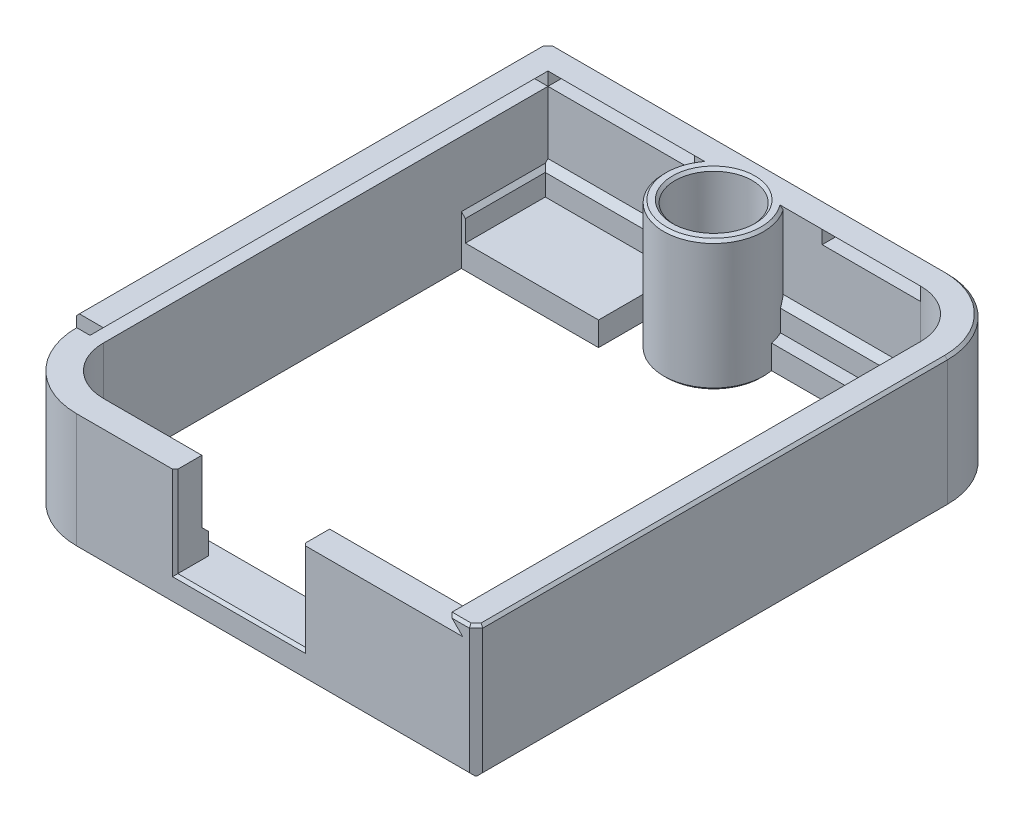
SolidWorks part; units mm, degrees
ref_plane "前视基准面" through (0, 0, 0) normal (0, 0, 1) x (1, 0, 0)
ref_plane "上视基准面" through (0, 0, 0) normal (0, 1, 0) x (1, 0, 0)
ref_plane "右视基准面" through (0, 0, 0) normal (1, 0, 0) x (0, 0, -1)
sketch "草图1" plane through (0, 0, 0) normal (0, 1, 0) x (1, 0, 0)
  line L0 (-23.4673, 10.3958) -> (6.5327, 10.3958)
  line L5 (12.1327, 4.7958) -> (12.1327, -30.6042)
  line L6 (-23.4673, 10.3958) -> (-23.4673, -25.0042)
  line L7 (-17.8673, -30.6042) -> (12.1327, -30.6042)
  arc A0 (6.5327, 10.3958) -> (12.1327, 4.7958) centre (6.5327, 4.7958) cw
  arc A1 (-17.8673, -30.6042) -> (-23.4673, -25.0042) centre (-17.8673, -25.0042) cw
extrude "凸台-拉伸1" add sketch "草图1" along normal blind 9.8
shell "抽壳1" thickness 2 removed face at (-5.6673, 9.8, 10.1042)
sketch "PCB实际占位" plane through (0, 2, 0) normal (0, 1, 0) x (1, 0, 0)
  line L4 (-21.1673, 7.8958) -> (9.8327, 7.8958)
  line L5 (-21.1673, 7.8958) -> (-21.1673, -28.1042)
  line L6 (-21.1673, -28.1042) -> (9.8327, -28.1042)
  line L7 (9.8327, 7.8958) -> (9.8327, -28.1042)
  dimension "D1" = 31
  dimension "D2" = 36
sketch "草图3" plane through (0, 2, 0) normal (0, 1, 0) x (1, 0, 0)
  line L0 (-21.1673, 7.8958) -> (-21.1673, 1.8958) construction
  line L1 (-21.1673, 7.8958) -> (-21.1673, -28.1042) construction
  line L2 (-21.1673, 1.8958) -> (-11.1673, 1.8958) construction
  line L3 (9.8327, 7.8958) -> (9.8327, 5.8958) construction
  line L4 (9.8327, 7.8958) -> (9.8327, -28.1042) construction
  line L5 (9.8327, 5.8958) -> (6.8327, 5.8958) construction
  line L6 (9.8327, -28.1042) -> (9.8327, -20.1042) construction
  line L7 (9.8327, -20.1042) -> (7.8327, -20.1042) construction
  line L8 (7.8327, -20.1042) -> (7.8327, -17.1042) construction
  line L9 (-21.1673, -28.1042) -> (-16.1673, -28.1042) construction
  line L10 (-21.1673, -28.1042) -> (9.8327, -28.1042) construction
  line L11 (-16.1673, -28.1042) -> (-16.1673, -26.1042) construction
  line L12 (-16.1673, -26.1042) -> (-14.1673, -26.1042) construction
  line L13 (-21.4673, -25.0042) -> (-17.8673, -25.0042) construction
  line L14 (10.1327, 4.7958) -> (6.5327, 4.7958) construction
  line L15 (-21.4673, 1.8958) -> (-21.4673, -25.0042)
  line L16 (-21.4673, 8.3958) -> (-21.4673, -25.0042) construction
  line L17 (-21.4673, 1.8958) -> (-11.1673, 1.8958)
  line L18 (-11.1673, 1.8958) -> (-11.1673, 6.8958)
  line L21 (10.1327, -28.6042) -> (10.1327, 4.7958) construction
  line L22 (10.1327, -17.1042) -> (7.8327, -17.1042)
  line L23 (7.8327, -17.1042) -> (7.8327, -20.1042)
  line L24 (7.8327, -20.1042) -> (10.1327, -20.1042)
  line L25 (10.1327, -20.1042) -> (10.1327, -27.1042)
  line L26 (10.1327, -27.1042) -> (-14.1673, -27.1042)
  line L27 (-14.1673, -27.1042) -> (-14.1673, -26.1042)
  line L28 (-14.1673, -26.1042) -> (-16.1673, -26.1042)
  line L29 (-16.1673, -26.1042) -> (-16.1673, -27.1042)
  line L30 (-16.1673, -27.1042) -> (-20.7914, -27.1042)
  line L31 (6.8327, 5.8958) -> (6.8327, 6.8958)
  line L32 (6.8327, 5.8958) -> (9.9595, 5.8988)
  line L33 (-11.1673, 6.8958) -> (6.8327, 6.8958)
  line L34 (10.1327, 4.7958) -> (10.1327, -17.1042)
  arc A1 (-21.4673, -25.0042) -> (-17.8673, -28.6042) centre (-17.8673, -25.0042) ccw construction
  arc A2 (-20.7914, -27.1042) -> (-21.4673, -25.0042) centre (-17.8673, -25.0042) cw
  arc A3 (10.1327, 4.7958) -> (6.5327, 8.3958) centre (6.5327, 4.7958) ccw construction
  arc A4 (-21.4673, -25.0042) -> (-17.8673, -28.6042) centre (-17.8673, -25.0042) ccw construction
  arc A5 (9.9595, 5.8988) -> (10.1327, 4.7958) centre (6.5327, 4.7958) cw
extrude "切除-拉伸1" cut sketch "草图3" against normal up to next
sketch "草图4" plane through (0, 2, 0) normal (0, 1, 0) x (1, 0, 0)
  line L0 (10.1327, 4.7958) -> (6.5327, 4.7958) construction
  line L1 (-21.4673, -25.0042) -> (-17.8673, -25.0042) construction
  line L2 (-21.4673, 1.8958) -> (-21.1673, 1.8958)
  line L3 (-21.1673, 7.8958) -> (-21.1673, -28.1042) construction
  line L4 (-11.1673, 1.8958) -> (-21.4673, 1.8958) construction
  line L5 (-21.1673, 1.8958) -> (-21.1673, 7.8958)
  line L6 (-21.1673, 7.8958) -> (9.8327, 7.8958) construction
  line L7 (6.5327, 8.3958) -> (-21.4673, 8.3958) construction
  line L8 (8.363, 7.8958) -> (-21.1673, 7.8958)
  line L9 (-21.4673, 1.8958) -> (-21.4673, 8.3958)
  line L10 (-21.4673, 8.3958) -> (-21.4673, -25.0042) construction
  line L11 (-21.4673, 8.3958) -> (-21.4673, 1.8958) construction
  line L12 (-21.4673, 8.3958) -> (6.5327, 8.3958)
  line L13 (9.8327, -17.1042) -> (10.1327, -17.1042)
  line L14 (9.8327, 7.8958) -> (9.8327, -28.1042) construction
  line L15 (7.8327, -17.1042) -> (10.1327, -17.1042) construction
  line L16 (10.1327, -17.1042) -> (10.1327, -20.1042)
  line L17 (10.1327, -20.1042) -> (9.8327, -20.1042)
  line L18 (10.1327, -20.1042) -> (7.8327, -20.1042) construction
  line L19 (9.8327, -20.1042) -> (9.8327, -17.1042)
  line L20 (-21.1673, -28.1042) -> (9.8327, -28.1042) construction
  line L21 (-19.6976, -28.1042) -> (10.1327, -28.1042)
  line L22 (10.1327, -28.6042) -> (10.1327, 4.7958) construction
  line L23 (10.1327, -28.1042) -> (10.1327, -28.6042)
  line L24 (10.1327, -28.6042) -> (-17.8673, -28.6042)
  arc A0 (8.363, 7.8958) -> (6.5327, 8.3958) centre (6.5327, 4.7958) ccw
  arc A1 (10.1327, 4.7958) -> (6.5327, 8.3958) centre (6.5327, 4.7958) ccw construction
  arc A2 (-17.8673, -28.6042) -> (-19.6976, -28.1042) centre (-17.8673, -25.0042) cw
extrude "凸台-拉伸2" add sketch "草图4" along normal blind 1.6
chamfer "倒角2" distance 0.3 1 edges at (-21.4673, 3.6, -5.1458)
chamfer "倒角3" distance 0.5 angle 45 2 edges at (7.4814, 3.6, -8.2685) (-7.3173, 3.6, -8.3958)
chamfer "倒角4" distance 0.3 angle 45 1 edges at (10.1327, 3.6, 18.6042)
chamfer "倒角5" distance 0.5 angle 45 2 edges at (-18.816, 3.6, 28.477) (-3.8673, 3.6, 28.6042)
sketch "草图5" plane through (0, 2, 0) normal (0, 1, 0) x (1, 0, 0)
  line L0 (9.8327, 7.8958) -> (9.8327, 7.4958) construction
  line L1 (9.8327, 7.8958) -> (9.8327, -28.1042) construction
  line L2 (9.8327, 7.4958) -> (-6.8673, 7.4958) construction
  line L3 (-6.8673, 10.3958) -> (-6.8673, 6.2458) construction
  line L4 (6.5327, 10.3958) -> (-23.4673, 10.3958) construction
  circle A0 centre (-6.8673, 6.2458) radius 3.75
extrude "凸台-拉伸3" add sketch "草图5" along normal up to surface (7.8 mm away) and the other way up to surface (2 mm away) up to face at (-5.6673, 9.8, 10.1042) other way up to face at (-3.7239, 0, 12.5511)
sketch "草图6" plane through (0, 9.8, 0) normal (0, 1, 0) x (1, 0, 0)
  circle A0 centre (-6.8673, 6.2458) radius 2.9
extrude "切除-拉伸2" cut sketch "草图6" against normal blind 7.8
sketch "草图7" plane through (0, 2, 0) normal (0, 1, 0) x (1, 0, 0)
  circle A0 centre (-6.8673, 6.2458) radius 1.65
extrude "切除-拉伸3" cut sketch "草图7" against normal through all
sketch "草图8" plane through (0, 9.8, 0) normal (0, 1, 0) x (1, 0, 0)
  line L0 (12.1327, -30.6042) -> (-0.8673, -30.6042) construction
  line L1 (-17.8673, -30.6042) -> (12.1327, -30.6042) construction
  line L2 (-23.4673, -25.0042) -> (-10.4673, -25.0042) construction
  line L4 (-0.8673, -30.6042) -> (-10.4673, -30.6042)
  line L5 (-0.8673, -30.6042) -> (-0.8673, -25.0042)
  line L6 (-0.8673, -25.0042) -> (-10.4673, -25.0042)
  line L7 (-10.4673, -30.6042) -> (-10.4673, -25.0042)
extrude "切除-拉伸5" cut sketch "草图8" against normal blind 7.8
sketch "草图10" plane through (0, 9.8, 0) normal (0, 1, 0) x (1, 0, 0)
  line L6 (-23.4673, -25.0042) -> (10.1327, -25.0042)
  line L7 (-23.4673, -25.0042) -> (-23.4673, -32.1399)
  line L8 (-23.4673, -32.1399) -> (10.1327, -32.1399)
  line L9 (10.1327, -25.0042) -> (10.1327, -32.1399)
extrude "切除-拉伸12" cut sketch "草图10" against normal blind 1
sketch "草图11" plane through (0, 0, 25.0042) normal (0, 0, 1) x (1, 0, 0)
  line L0 (-21.4673, 9.8) -> (-21.4673, 8.8)
  line L1 (-17.8673, 8.8) -> (-23.4673, 8.8) construction
  line L2 (-21.4673, 9.8) -> (-21.4673, 4.1) construction
  line L3 (-21.4673, 8.8) -> (-22.4673, 8.8)
  line L4 (-22.4673, 8.8) -> (-21.4673, 9.8)
extrude "切除-拉伸15" cut sketch "草图11" against normal blind 33.4
sketch "草图12" plane through (0, 0, 30.6042) normal (0, 0, 1) x (1, 0, 0)
  line L0 (10.1327, 9.8) -> (10.1327, 8.8)
  line L1 (10.1327, 8.8) -> (11.1327, 8.8)
  line L2 (11.1327, 8.8) -> (10.1327, 9.8)
extrude "切除-拉伸16" cut sketch "草图12" against normal up to vertex (35.4 mm away) up to point (10.1327, 9.8, -4.7958)
sketch "草图13" plane through (-21.4673, 0, 0) normal (1, 0, 0) x (0, 0, -1)
  line L0 (10.3958, 9.8) -> (8.3958, 9.8) construction
  line L1 (10.3958, 9.8) -> (4.7958, 9.8) construction
  line L2 (8.3958, 9.8) -> (8.3958, 8.8)
  line L3 (8.3958, 8.8) -> (9.3958, 8.8)
  line L4 (9.3958, 8.8) -> (8.3958, 9.8)
extrude "切除-拉伸18" cut sketch "草图13" along normal blind 11
sketch "草图14" plane through (-0.8673, 0, 0) normal (-1, 0, 0) x (0, 0, 1)
  line L0 (-10.3958, 9.8) -> (-8.3958, 9.8) construction
  line L1 (-10.3958, 9.8) -> (25.0042, 9.8) construction
  line L2 (-8.3958, 9.8) -> (-8.3958, 8.8)
  line L3 (-8.3958, 8.8) -> (-9.3958, 8.8)
  line L4 (-9.3958, 8.8) -> (-8.3958, 9.8)
extrude "切除-拉伸19" cut sketch "草图14" against normal up to vertex (7.4 mm away) up to point (6.5327, 9.8, -8.3958)
sketch "草图15" plane through (0, 2, 0) normal (0, 1, 0) x (1, 0, 0)
  line L0 (-20.7914, -27.1042) -> (-16.1673, -27.1042) construction
  line L1 (-16.6905, -27.1042) -> (10.1327, -27.1042)
  line L2 (-16.6905, -27.1042) -> (-16.6905, -15.4112)
  line L3 (-16.6905, -15.4112) -> (10.1327, -15.4112)
  line L4 (10.1327, -27.1042) -> (10.1327, -15.4112)
  line L5 (10.1327, -30.6042) -> (10.1327, 4.7958) construction
extrude "去除小托" cut sketch "草图15" against normal through all and the other way through all
chamfer "倒角6" distance 0.2 angle 45 19 edges at (-21.8271, 0, 28.964) (-2.8673, 0, 30.6042) (12.1327, 0, 12.9042) (10.4925, 0, -8.7555) (-8.4673, 0, -10.3958) (-23.4673, 0, 7.3042) (6.8327, 0, -6.3958) (8.3961, 0, -5.8973) (10.0891, 0, -5.354) (10.1327, 0, 11.1542) (-5.3293, 0, 27.1042) (-21.2942, 0, 26.1073) (-21.4673, 0, 11.5542) (-16.3173, 0, -1.8958) (-11.1673, 0, -4.3958) (-10.8639, 0, -6.8958) (-6.8673, 0, -2.4958) (1.8293, 0, -6.8958) (-6.8673, 0, -4.5958)
chamfer "倒角7" distance 0.5 angle 45 2 edges at (-23.4673, 5, -10.3958) (12.1327, 5, 30.6042)
chamfer "倒角8" distance 0.2 angle 45 8 edges at (-6.8673, 9.8, -3.3458) (-6.8673, 9.8, -2.4958) (11.8827, 9.8, 30.3542) (12.1327, 9.8, 12.6542) (10.4925, 9.8, -8.7555) (-8.2173, 9.8, -10.3958) (-23.2173, 9.8, -10.1458) (-23.4673, 9.8, 7.5542)
chamfer "倒角11" distance 0.2 angle 45 3 edges at (-0.8673, 5.4, 30.6042) (-5.6673, 2, 30.6042) (-10.4673, 5.4, 30.6042)
chamfer "倒角12" distance 0.2 angle 45 1 edges at (10.7413, 9.8, 30.6042)
